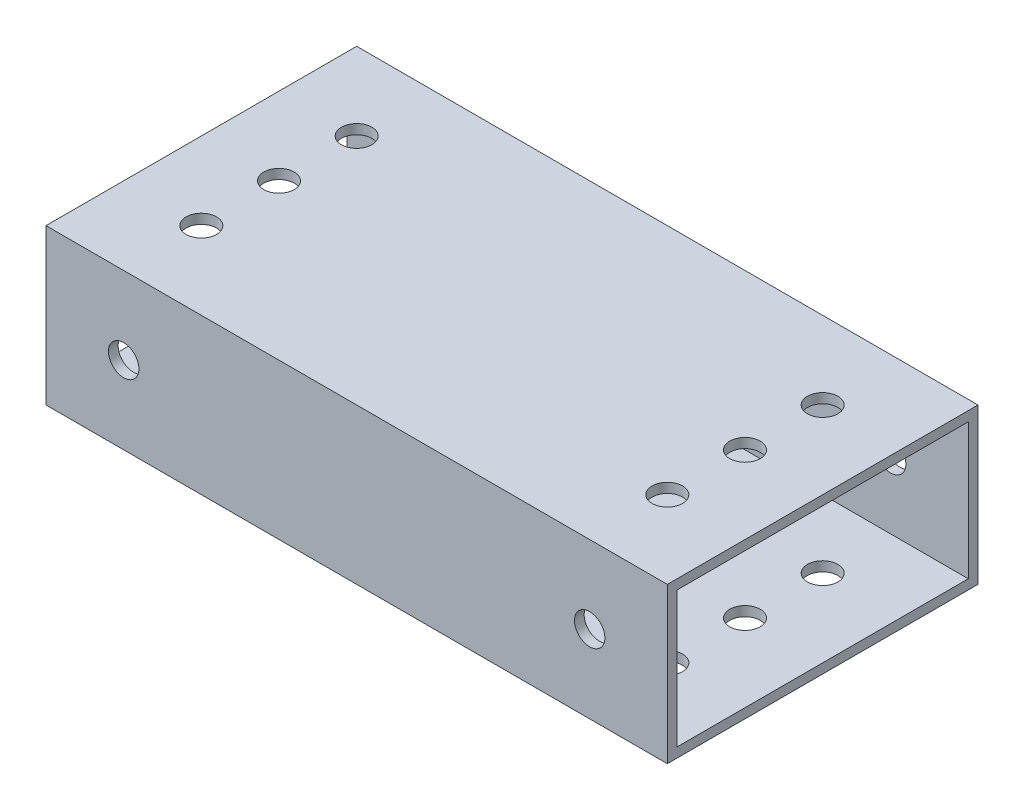
SolidWorks part; units mm, degrees
material "6061-T6 (SS)"
ref_plane "Front Plane" through (0, 0, 0) normal (0, 0, 1) x (1, 0, 0)
ref_plane "Top Plane" through (0, 0, 0) normal (0, 1, 0) x (1, 0, 0)
ref_plane "Right Plane" through (0, 0, 0) normal (1, 0, 0) x (0, 0, -1)
sketch "Sketch1" plane through (0, 0, 0) normal (1, 0, 0) x (0, 0, -1)
  line L1 (0, 0) -> (50.8, 0)
  line L2 (0, 0) -> (0, 25.4)
  line L3 (0, 25.4) -> (50.8, 25.4)
  line L4 (50.8, 0) -> (50.8, 25.4)
  dimension "D1" = 25.4
  dimension "D2" = 50.8
extrude "Boss-Extrude1" add sketch "Sketch1" along normal mid plane 101.6
shell "Shell1" thickness 1.5875 removed face at (-50.8, 12.7, -25.4) removed face at (50.8, 12.7, -25.4)
sketch "Sketch2" plane through (0, 25.4, 0) normal (0, 1, 0) x (1, 0, 0)
  line L0 (-38.1, 50.8) -> (-38.1, 0) construction
  line L1 (50.8, 50.8) -> (-50.8, 50.8) construction
  line L2 (50.8, 0) -> (-50.8, 0) construction
  line L3 (-50.8, 50.8) -> (-50.8, 0) construction
  circle A0 centre (-38.1, 25.4) radius 2.4892
  circle A1 centre (-38.1, 12.7) radius 2.4892
  circle A2 centre (-38.1, 38.1) radius 2.4892
  dimension "D1" = 4.9784
  dimension "D2" = 12.7
  dimension "D3" = 12.7
  dimension "D4" = 12.7
extrude "Cut-Extrude1" cut sketch "Sketch2" against normal through all
sketch "Sketch3" plane through (0, 0, 0) normal (0, 0, 1) x (1, 0, 0)
  line L0 (50.8, 25.4) -> (-50.8, 25.4) construction
  line L1 (-50.8, 25.4) -> (-50.8, 0) construction
  circle A0 centre (-38.1, 12.7) radius 2.4892
  dimension "D3" = 4.9784
  dimension "D1" = 12.7
  dimension "D2" = 12.7
extrude "Cut-Extrude2" cut sketch "Sketch3" against normal through all
mirror "Mirror1" about plane through (0, 0, 0) normal (1, 0, 0) of "Cut-Extrude2", "Cut-Extrude1"
